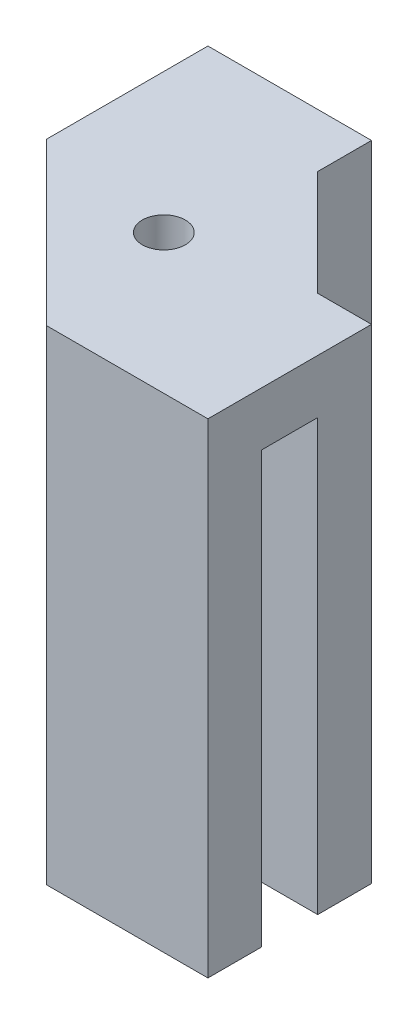
SolidWorks part; units mm, degrees
ref_plane "Front Plane" through (0, 0, 0) normal (0, 0, 1) x (1, 0, 0)
ref_plane "Top Plane" through (0, 0, 0) normal (0, 1, 0) x (1, 0, 0)
ref_plane "Right Plane" through (0, 0, 0) normal (1, 0, 0) x (0, 0, -1)
sketch "Sketch1" plane through (0, 0, 0) normal (0, 1, 0) x (1, 0, 0)
  line L0 (0, 0) -> (0, 25.4) construction
  line L1 (0, 0) -> (35.921, 35.921) construction
  line L2 (22.098, 9.652) -> (9.652, 22.098)
  line L3 (9.652, 22.098) -> (9.652, 28.448)
  line L4 (9.652, 28.448) -> (3.302, 28.448)
  line L5 (3.302, 28.448) -> (3.302, 15.748)
  line L6 (3.302, 15.748) -> (-3.302, 15.748)
  line L7 (-3.302, 28.448) -> (-3.302, 15.748)
  line L8 (3.302, 15.748) -> (9.652, 22.098) construction
  line L9 (-3.302, 28.448) -> (-9.652, 28.448)
  line L10 (-9.652, 28.448) -> (-9.652, 9.398)
  line L11 (-9.652, 9.398) -> (9.398, -9.652)
  line L12 (0, 0) -> (-35.921, -35.921) construction
  line L13 (-3.302, 15.748) -> (-9.652, 9.398) construction
  line L14 (15.748, -3.302) -> (9.398, -9.652) construction
  line L15 (15.748, 3.302) -> (22.098, 9.652) construction
  line L16 (0, 0) -> (25.4, 0) construction
  line L17 (28.448, -9.652) -> (9.398, -9.652)
  line L18 (28.448, -3.302) -> (28.448, -9.652)
  line L19 (28.448, -3.302) -> (15.748, -3.302)
  line L20 (15.748, 3.302) -> (15.748, -3.302)
  line L21 (28.448, 3.302) -> (15.748, 3.302)
  line L22 (28.448, 9.652) -> (28.448, 3.302)
  line L23 (22.098, 9.652) -> (28.448, 9.652)
  point P3 (15.748, 0)
  point P11 (0, 15.748)
  point P26 (15.875, 15.875)
  dimension "D1" = 45
  dimension "D2" = 25.4
  dimension "D3" = 50.8
  dimension "D4" = 6.604
  dimension "D6" = 6.35
  dimension "D7" = 45
  dimension "D5" = 12.7
  dimension "D8" = 25.4
extrude "Boss-Extrude1" add sketch "Sketch1" along normal blind 50.8
hole_wizard "Tap Drill for 1/4-20 Tap1" positions "Sketch2" profile "Sketch3" hole size "1/4-20" standard "ANSI Inch" end condition through all
sketch "Sketch2" plane through (0, 50.8, 0) normal (0, 1, 0) x (1, 0, 0)
  line L0 (0, 0) -> (6.7953, 6.7953) construction
  line L1 (6.7953, 6.7953) -> (15.748, 3.302) construction
  line L3 (6.7953, 6.7953) -> (3.302, 15.748) construction
  point P2 (6.7953, 6.7953)
sketch "Sketch3" plane through (6.7953, 50.8, -6.7953) normal (1, 0, 0) x (0, 0, 1)
  line L0 (0, 0) -> (0, 50.8)
  line L1 (0, 50.8) -> (2.54, 50.8)
  line L2 (2.54, 50.8) -> (2.54, 0)
  line L5 (2.54, 0) -> (0, 0)
  line L11 (0, -6.35) -> (0, 107.95) construction
  dimension "Thru Hole Dia." = 5.08
  dimension "Thru Hole Depth" = 50.8
sketch "Sketch4" plane through (0, 50.8, 0) normal (0, 1, 0) x (1, 0, 0)
  line L0 (-3.302, 28.448) -> (3.302, 28.448)
  line L1 (28.448, 3.302) -> (28.448, -3.302)
  line L16 (9.652, 22.098) -> (9.652, 28.448)
  line L17 (9.652, 28.448) -> (3.302, 28.448)
  line L18 (3.302, 28.448) -> (3.302, 15.748)
  line L19 (3.302, 15.748) -> (-3.302, 15.748)
  line L20 (-3.302, 15.748) -> (-3.302, 28.448)
  line L21 (-3.302, 28.448) -> (-9.652, 28.448)
  line L22 (-9.652, 28.448) -> (-9.652, 9.398)
  line L23 (-9.652, 9.398) -> (9.398, -9.652)
  line L24 (9.398, -9.652) -> (28.448, -9.652)
  line L25 (28.448, -9.652) -> (28.448, -3.302)
  line L26 (28.448, -3.302) -> (15.748, -3.302)
  line L27 (15.748, -3.302) -> (15.748, 3.302)
  line L28 (15.748, 3.302) -> (28.448, 3.302)
  line L29 (28.448, 3.302) -> (28.448, 9.652)
  line L30 (28.448, 9.652) -> (22.098, 9.652)
  line L31 (22.098, 9.652) -> (9.652, 22.098)
  line L32 (9.652, 22.098) -> (9.652, 28.448)
  line L33 (9.652, 28.448) -> (3.302, 28.448)
  line L37 (-3.302, 28.448) -> (-9.652, 28.448)
  line L38 (-9.652, 28.448) -> (-9.652, 9.398)
  line L39 (-9.652, 9.398) -> (9.398, -9.652)
  line L40 (9.398, -9.652) -> (28.448, -9.652)
  line L41 (28.448, -9.652) -> (28.448, -3.302)
  line L45 (28.448, 3.302) -> (28.448, 9.652)
  line L46 (28.448, 9.652) -> (22.098, 9.652)
  line L47 (22.098, 9.652) -> (9.652, 22.098)
  circle A0 centre (6.7953, 6.7953) radius 2.54 construction
  circle A1 centre (6.7953, 6.7953) radius 2.54
  dimension "D1" = 0
extrude "Boss-Extrude2" add sketch "Sketch4" along normal blind 6.35
equation "\"Material_thickness\"= 0.25in"
equation "\"Tollerence\"= 0.01in"
equation "\"D4@Sketch1\"=\"Material_thickness\"+\"Tollerence\""
equation "\"Height\"= \"box_height\" - 0.25in"
equation "\"D1@Boss-Extrude1\"=\"Height\""
equation "\"D5@Sketch1\"=0.5"
equation "\"box_width\" = 7in"
equation "\"box_other_width\" = 6in"
equation "\"box_height\" = 2.25in"
